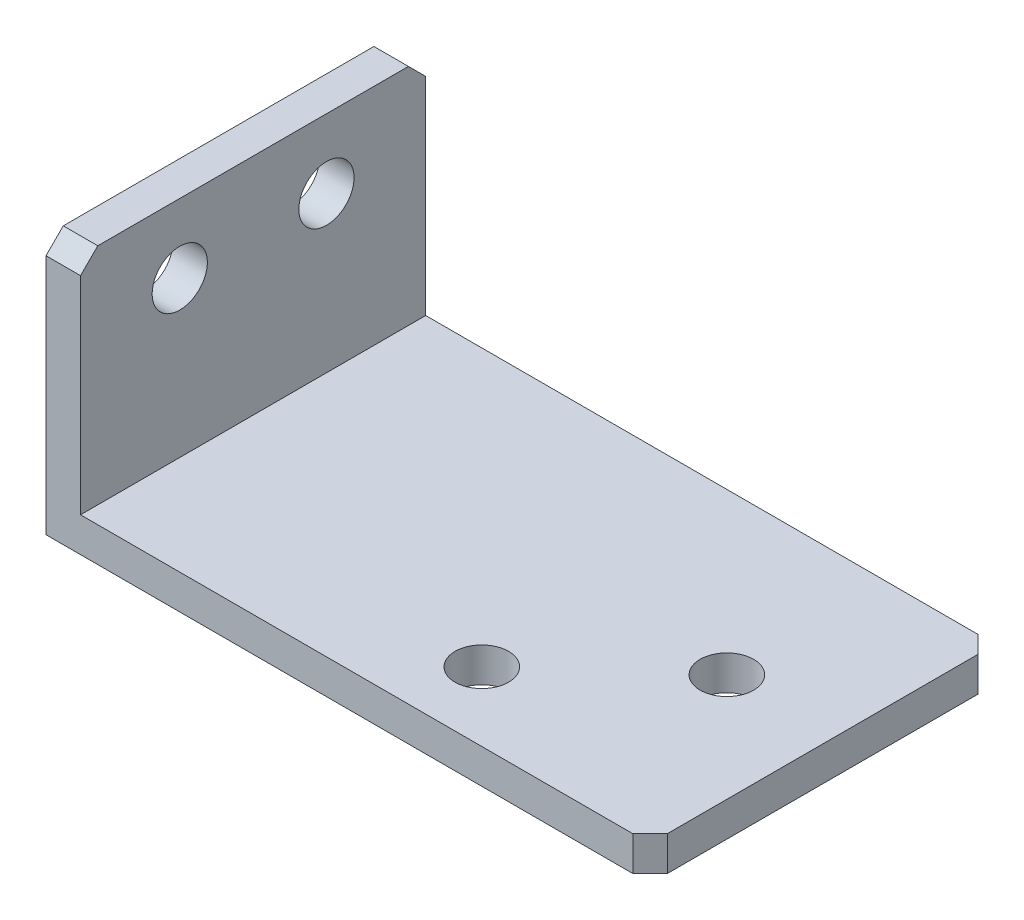
SolidWorks part; units mm, degrees
material "6063-T5"
ref_plane "Спереди" through (0, 0, 0) normal (0, 0, 1) x (1, 0, 0)
ref_plane "Сверху" through (0, 0, 0) normal (0, 1, 0) x (1, 0, 0)
ref_plane "Справа" through (0, 0, 0) normal (1, 0, 0) x (0, 0, -1)
sketch "Sketch1" plane through (0, 0, 0) normal (0, 0, 1) x (1, 0, 0)
  line L0 (0, 0) -> (35, 0)
  line L1 (35, 0) -> (35, 2)
  line L2 (35, 2) -> (2, 2)
  line L3 (2, 2) -> (2, 15)
  line L4 (2, 15) -> (0, 15)
  line L5 (0, 15) -> (0, 0)
  dimension "D1" = 35
  dimension "D2" = 15
  dimension "D4" = 2
extrude "Base" add sketch "Sketch1" along normal blind 20
sketch "Sketch5" plane through (0, 2, 0) normal (0, 1, 0) x (1, 0, 0)
  line L0 (0, -20) -> (0, 0) construction
  line L2 (35, -20) -> (2, -20) construction
  circle A0 centre (21.25, -16) radius 1.55
  circle A1 centre (28.75, -9.3) radius 1.55
  dimension "D3" = 3.1
  dimension "D1" = 4
  dimension "D2" = 6.7
  dimension "D4" = 7.5
  dimension "D5" = 21.25
extrude "CableChainSide" cut sketch "Sketch5" against normal through all
chamfer "Chamfer1" distance 1 angle 45 4 edges at (35, 1, 0) (1, 15, 0) (1, 15, 20) (35, 1, 20)
hole_wizard "Ø3.2 (3.2) Diameter Hole1" positions "Sketch6" profile "Sketch7" hole size "Ø3.2" standard "ANSI Metric" end condition through all
sketch "Sketch6" plane through (0, 0, 0) normal (-1, 0, 0) x (0, 0, 1)
  line L1 (20, 0) -> (0, 0) construction
  line L3 (10, 0) -> (10, 2.8485) construction
  point P0 (5.75, 11)
  point P2 (14.25, 11)
  point P16 (0, 0)
  dimension "D1" = 8.5
  dimension "D3" = 11
sketch "Sketch7" plane through (0, 11, 5.75) normal (0, 1, 0) x (0, 0, 1)
  line L0 (0, 0) -> (0, 35)
  line L1 (0, 35) -> (1.6, 35)
  line L2 (1.6, 35) -> (1.6, 0)
  line L5 (1.6, 0) -> (0, 0)
  line L11 (0, -6.35) -> (0, 107.95) construction
  dimension "Thru Hole Dia." = 3.2
  dimension "Thru Hole Depth" = 35
